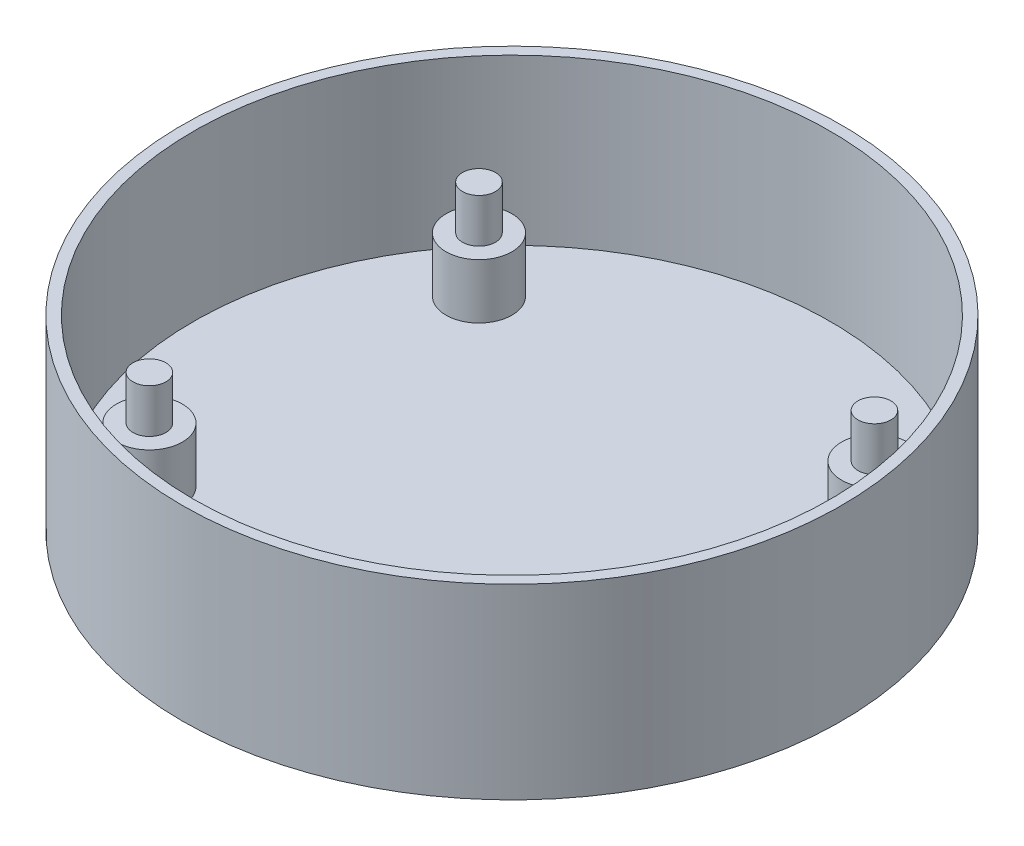
SolidWorks part; units mm, degrees
ref_plane "Front Plane" through (0, 0, 0) normal (0, 0, 1) x (1, 0, 0)
ref_plane "Top Plane" through (0, 0, 0) normal (0, 1, 0) x (1, 0, 0)
ref_plane "Right Plane" through (0, 0, 0) normal (1, 0, 0) x (0, 0, -1)
sketch "Sketch1" plane through (0, 0, 0) normal (0, 1, 0) x (1, 0, 0)
  circle A0 centre (0, 0) radius 30
extrude "Boss-Extrude1" add sketch "Sketch1" along normal blind 17
sketch "Sketch2" plane through (0, 17, 0) normal (0, 1, 0) x (1, 0, 0)
  circle A0 centre (0, 0) radius 29
extrude "Cut-Extrude1" cut sketch "Sketch2" against normal blind 15
sketch "Sketch3" plane through (0, 2, 0) normal (0, 1, 0) x (1, 0, 0)
  circle A0 centre (-18, 15) radius 3
  circle A1 centre (-18, -15) radius 3
  circle A2 centre (18, -15) radius 3
  circle A3 centre (18, 15) radius 3
  point P0 (0, 0)
extrude "Boss-Extrude5" add sketch "Sketch3" along normal blind 5
sketch "Sketch4" plane through (0, 7, 0) normal (0, 1, 0) x (1, 0, 0)
  circle A1 centre (-18, 15) radius 1.5
  circle A2 centre (-18, -15) radius 1.5
  circle A3 centre (18, 15) radius 1.5
  circle A4 centre (18, -15) radius 1.5
extrude "Boss-Extrude6" add sketch "Sketch4" along normal blind 4
